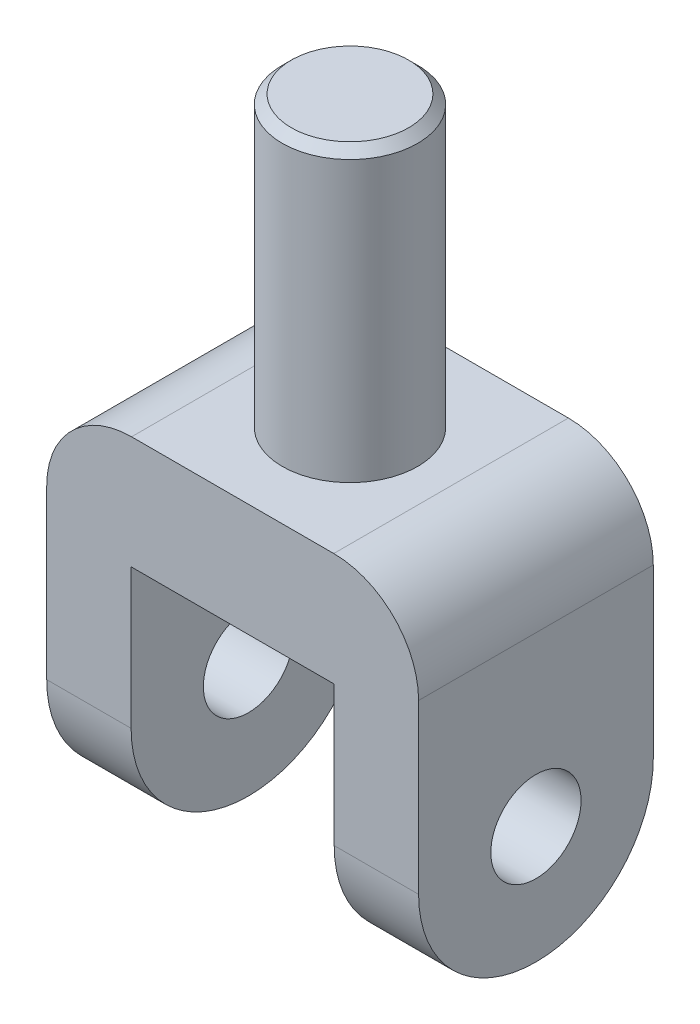
SolidWorks part; units mm, degrees
ref_plane "Alzado" through (0, 0, 0) normal (0, 0, 1) x (1, 0, 0)
ref_plane "Planta" through (0, 0, 0) normal (0, 1, 0) x (1, 0, 0)
ref_plane "Vista lateral" through (0, 0, 0) normal (1, 0, 0) x (0, 0, -1)
sketch "Sketch2" plane through (0, 0, 0) normal (0, 0, 1) x (1, 0, 0)
  line L0 (0, 0.3793) -> (0, 105.156) construction
  line L1 (52.324, 0) -> (5.9238, 0) construction
  line L3 (19.05, 23.876) -> (19.05, 105.156)
  line L4 (28.448, 23.876) -> (-28.448, 23.876)
  line L5 (52.324, 0) -> (52.324, -80.264)
  line L6 (52.324, -80.264) -> (28.575, -80.264)
  line L7 (0, 23.876) -> (0, -4.5183) construction
  line L8 (28.575, -80.264) -> (28.575, -7.874)
  line L9 (28.575, -7.874) -> (-28.575, -7.874)
  line L13 (19.05, 105.156) -> (-19.05, 105.156)
  line L14 (-19.05, 23.876) -> (-19.05, 105.156)
  line L15 (-28.575, -80.264) -> (-28.575, -7.874)
  line L16 (-52.324, -80.264) -> (-28.575, -80.264)
  line L17 (-52.324, 0) -> (-52.324, -80.264)
  line L20 (0, 4.24) -> (0, 4.7129) construction
  arc A0 (52.324, 0) -> (28.448, 23.876) centre (28.448, 0) ccw
  arc A1 (-52.324, 0) -> (-28.448, 23.876) centre (-28.448, 0) cw
  point P22 (0, -7.874)
  dimension "D1" = 23.876
  dimension "D2" = 57.15
  dimension "D3" = 104.14
  dimension "D4" = 81.28
  dimension "D5" = 104.648
  dimension "D6" = 31.75
  dimension "D7" = 19.05
extrude "Boss-Extrude1" add sketch "Sketch2" along normal blind 33.02 and the other way blind 33.02 contours A1 L17 L16 L15 L9 L8 L6 L5 A0 L4 region at (23.749, 22.3996, 0)
extrude "Boss-Extrude3" add sketch "Sketch2<6>" along normal blind 19.05 and the other way blind 19.05 contours L14 L4 L3 L13 region at (0, 64.516, 0)
sketch "Sketch2<6>" plane through (0, 0, 0) normal (0, 0, 1) x (1, 0, 0) same geometry as "Sketch2"
sketch "Sketch8" plane through (0, 105.156, 0) normal (0, 1, 0) x (1, 0, 0)
  line L0 (19.05, 19.05) -> (19.05, -19.05) construction
  circle A0 centre (0, 0) radius 19.05
extrude "Cut-Extrude1" cut sketch "Sketch8" against normal blind 81.28 flip side to cut
chamfer "Chamfer2" distance 2.54 angle 45 1 edges at (0, 105.156, 19.05)
fillet "Fillet2" radius 33.02 4 edges at (-40.4495, -80.264, -33.02) (40.4495, -80.264, -33.02) (40.4495, -80.264, 33.02) (-40.4495, -80.264, 33.02)
hole_wizard "Hole1" positions "Sketch9" profile "Sketch10" legacy end condition through all
sketch "Sketch9" plane through (52.324, 0, 0) normal (1, 0, 0) x (0, 0, -1)
  point P0 (0, -47.244)
  point P1 (0, 0)
  point P3 (0, 0)
  dimension "D1" = 33.02
sketch "Sketch10" plane through (52.324, -47.244, 0) normal (0, 1, 0) x (0, 0, -1)
  line L0 (0, 0) -> (0, 104.648)
  line L1 (0, 104.648) -> (12.7, 104.648)
  line L2 (12.7, 104.648) -> (12.7, 0)
  line L3 (12.7, 0) -> (0, 0)
  line L4 (0, 110) -> (0, -10) construction
  dimension "Diameter" = 25.4
  dimension "Depth" = 104.648
